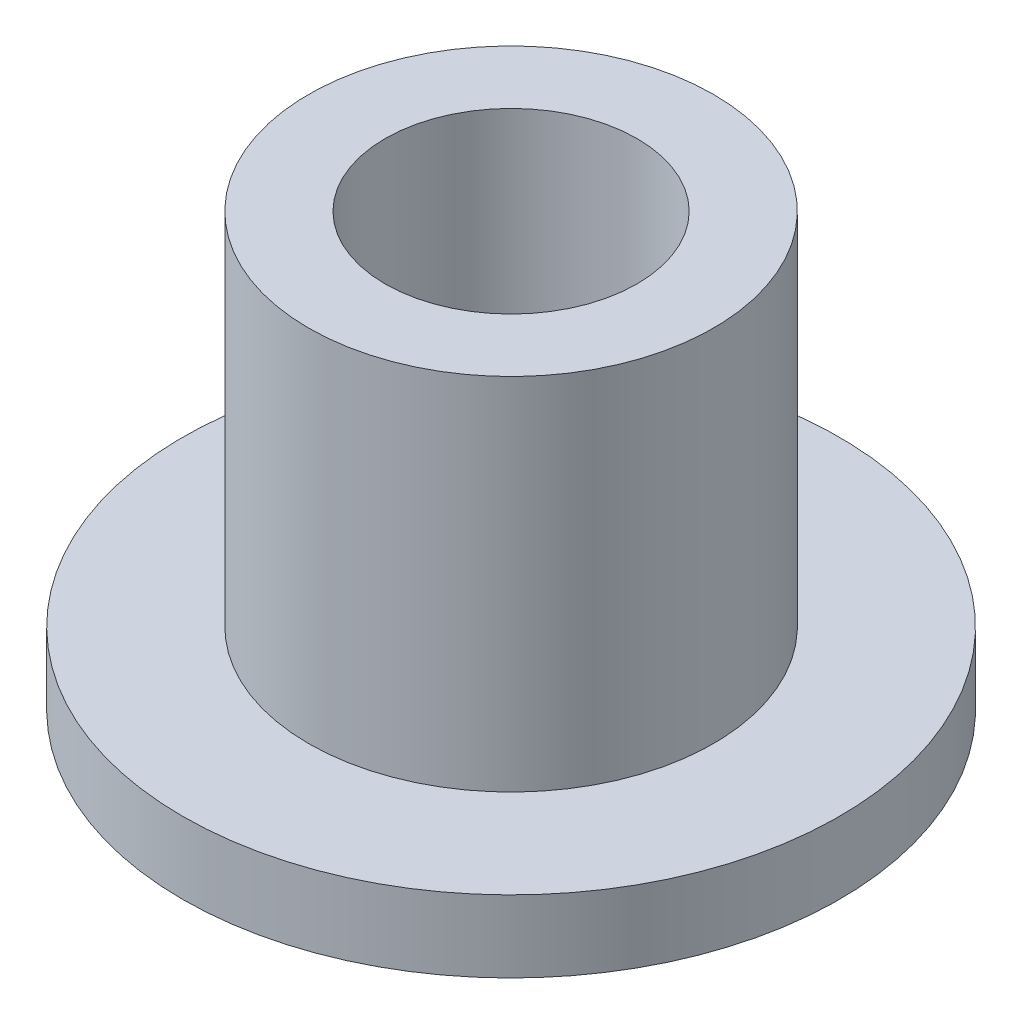
SolidWorks part; units mm, degrees
ref_plane "Front Plane" through (0, 0, 0) normal (0, 0, 1) x (1, 0, 0)
ref_plane "Top Plane" through (0, 0, 0) normal (0, 1, 0) x (1, 0, 0)
ref_plane "Right Plane" through (0, 0, 0) normal (1, 0, 0) x (0, 0, -1)
sketch "Sketch1" plane through (0, 0, 0) normal (0, 1, 0) x (1, 0, 0)
  circle A0 centre (0, 0) radius 14.2875
  circle A1 centre (0, 0) radius 6.35 construction
  circle A2 centre (0, 0) radius 23.1775
  circle A4 centre (0, 0) radius 8.89
  dimension "D1" = 28.575
  dimension "D2" = 12.7
  dimension "D3" = 8.89
  dimension "D4" = 2.54
extrude "Boss-Extrude2" add sketch "Sketch1" against normal blind 5.08 contours A2 A0 region at (-22.5219, 0, 0)
extrude "Boss-Extrude3" add sketch "Sketch1<4>" along normal blind 25.4 and the other way up to surface (5.08 mm away) contours A0 A4 region at (-13.8834, 0, 0) other way up to face at (0, -5.08, 14.2875)
sketch "Sketch1<4>" plane through (0, 0, 0) normal (0, 1, 0) x (1, 0, 0) same geometry as "Sketch1"
